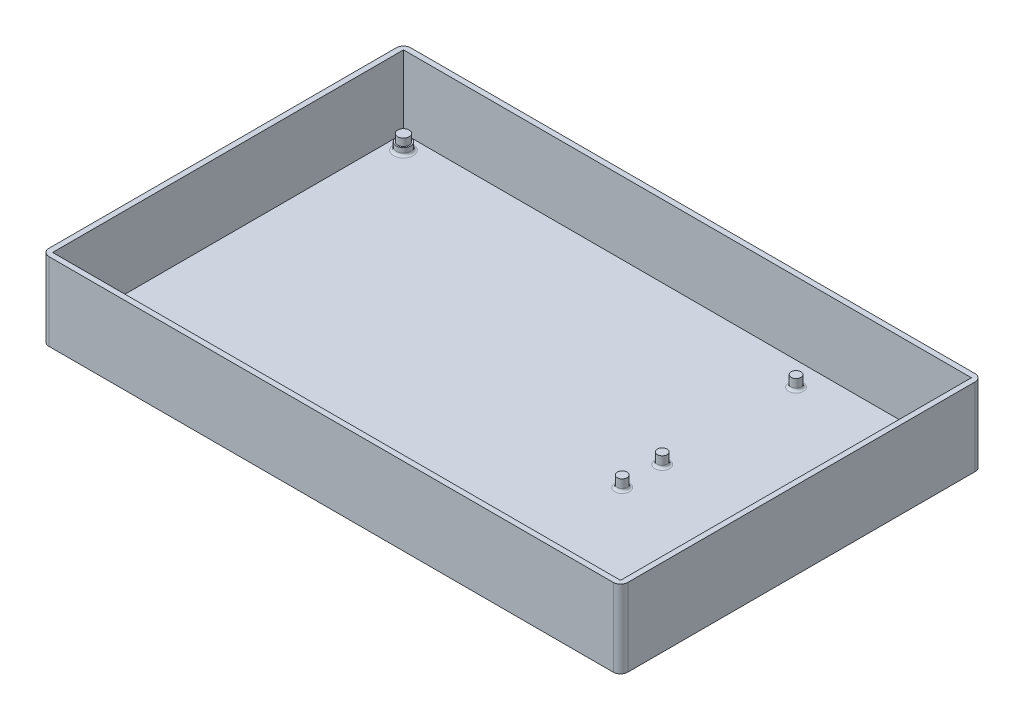
SolidWorks part; units mm, degrees
ref_plane "Front Plane" through (0, 0, 0) normal (0, 0, 1) x (1, 0, 0)
ref_plane "Top Plane" through (0, 0, 0) normal (0, 1, 0) x (1, 0, 0)
ref_plane "Right Plane" through (0, 0, 0) normal (1, 0, 0) x (0, 0, -1)
sketch "Sketch1" plane through (0, 0, 0) normal (0, 1, 0) x (1, 0, 0)
  line L0 (80, 0) -> (80, 1.5) construction
  line L1 (0, 0) -> (160, 0)
  line L2 (0, 0) -> (0, 100)
  line L3 (0, 100) -> (160, 100)
  line L4 (160, 0) -> (160, 100)
  line L5 (80, 1.5) -> (0, 1.5) construction
  line L6 (0, 50) -> (1.5, 50) construction
  line L7 (1.5, 50) -> (1.5, 0) construction
  line L9 (1.5, 1.5) -> (158.5, 1.5)
  line L10 (1.5, 1.5) -> (1.5, 98.5)
  line L11 (1.5, 98.5) -> (158.5, 98.5)
  line L12 (158.5, 1.5) -> (158.5, 98.5)
  dimension "D1" = 100
  dimension "D2" = 160
  dimension "D3" = 157
  dimension "D4" = 97
extrude "Boss-Extrude1" add sketch "Sketch1" along normal blind 20 contours L10 L9 L12 L11 | L2 L1 L4 L3
sketch "Sketch2" plane through (0, 0, 0) normal (0, -1, 0) x (1, 0, 0)
  line L1 (0, 0) -> (160, 0)
  line L2 (0, 0) -> (0, -100)
  line L3 (0, -100) -> (160, -100)
  line L4 (160, 0) -> (160, -100)
extrude "Boss-Extrude2" add sketch "Sketch2" along normal blind 1.5
sketch "Sketch3" plane through (0, 0, 0) normal (0, 1, 0) x (1, 0, 0)
  line L0 (1.5, 1.5) -> (5.5, 1.5) construction
  line L1 (1.5, 1.5) -> (158.5, 1.5) construction
  line L2 (5.5, 1.5) -> (5.5, 5.5) construction
  line L3 (0, 50) -> (160, 50) construction
  line L4 (0, 0) -> (0, 100) construction
  line L5 (160, 0) -> (160, 100) construction
  line L8 (5.5, 5.5) -> (94.5, 5.5) construction
  circle A0 centre (5.5, 5.5) radius 2
  circle A3 centre (5.5, 94.5) radius 2
  circle A4 centre (94.5, 5.5) radius 2
  point P16 (0, 0)
  dimension "D1" = 4
  dimension "D3" = 89
extrude "Boss-Extrude3" add sketch "Sketch3" along normal blind 2
sketch "Sketch4" plane through (0, 2, 0) normal (0, 1, 0) x (1, 0, 0)
  line L0 (0, 50) -> (158.5, 50) construction
  line L1 (0, 0) -> (0, 100) construction
  line L2 (158.5, 1.5) -> (158.5, 98.5) construction
  circle A0 centre (5.5, 5.5) radius 1.6
  circle A1 centre (94.5, 5.5) radius 1.6
  circle A2 centre (5.5, 94.5) radius 1.6
  point P16 (0, 0)
  dimension "D1" = 3.2
  dimension "D2" = 3.2
extrude "Boss-Extrude4" add sketch "Sketch4" along normal blind 2
sketch "Sketch5" plane through (0, 0, 0) normal (0, 1, 0) x (1, 0, 0)
  line L0 (1.5, 50) -> (96.5, 50) construction
  line L1 (1.5, 1.5) -> (1.5, 98.5) construction
  line L2 (96.5, 50) -> (96.5, 98.5) construction
  line L3 (1.5, 98.5) -> (158.5, 98.5) construction
  line L4 (96.5, 74.25) -> (116.5, 74.25) construction
  line L5 (96.5, 50) -> (96.5, 1.5) construction
  line L6 (1.5, 1.5) -> (158.5, 1.5) construction
  line L7 (96.5, 25.75) -> (116.5, 25.75) construction
  line L8 (116.5, 74.25) -> (116.5, 92.0274) construction
  line L9 (116.5, 92.0274) -> (116.5, 55.0274) construction
  line L10 (116.5, 92.0274) -> (153.5, 92.0274) construction
  line L11 (116.5, 55.0274) -> (153.5, 55.0274) construction
  line L12 (116.5, 25.75) -> (116.5, 43.9689) construction
  line L13 (116.5, 43.9689) -> (116.5, 6.9689) construction
  line L14 (116.5, 43.9689) -> (153.5, 43.9689) construction
  line L15 (153.5, 43.9689) -> (153.5, 6.9689) construction
  circle A0 centre (116.5, 92.0274) radius 1.35
  circle A1 centre (116.5, 55.0274) radius 1.35
  circle A2 centre (153.5, 55.0274) radius 1.35
  circle A3 centre (153.5, 92.0274) radius 1.35
  circle A4 centre (116.5, 43.9689) radius 1.35
  circle A5 centre (153.5, 43.9689) radius 1.35
  circle A6 centre (116.5, 6.9689) radius 1.35
  circle A7 centre (153.5, 6.9689) radius 1.35
  dimension "D4" = 2.7
  dimension "D1" = 95
  dimension "D2" = 20
  dimension "D3" = 37
  dimension "D5" = 37
  dimension "D6" = 37
extrude "Boss-Extrude5" add sketch "Sketch5" along normal blind 3
fillet "Fillet1" radius 0.7 11 edges at (153.5, 0, -8.3189) (94.5, 0, -7.5) (116.5, 0, -8.3189) (5.5, 0, -7.5) (5.5, 0, -96.5) (153.5, 0, -45.3189) (116.5, 0, -45.3189) (116.5, 0, -56.3774) (153.5, 0, -56.3774) (153.5, 0, -93.3774) (116.5, 0, -93.3774)
fillet "Fillet2" radius 2 4 edges at (160, 9.25, -100) (0, 9.25, -100) (0, 9.25, 0) (160, 9.25, 0)
